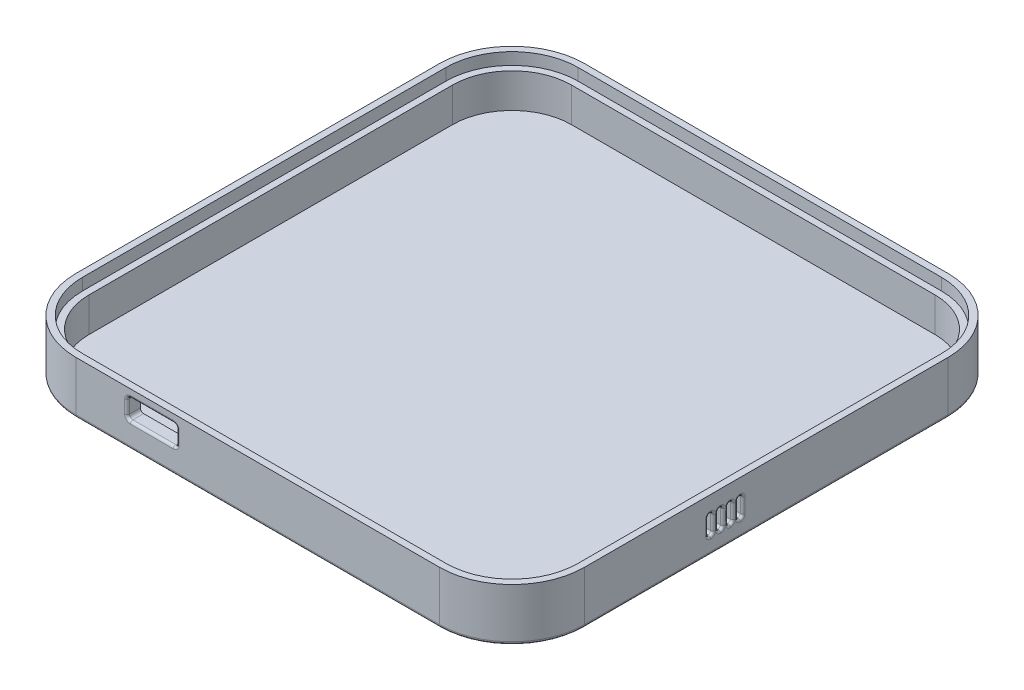
SolidWorks part; units mm, degrees
ref_plane "Front Plane" through (0, 0, 0) normal (0, 0, 1) x (1, 0, 0)
ref_plane "Top Plane" through (0, 0, 0) normal (0, 1, 0) x (1, 0, 0)
ref_plane "Right Plane" through (0, 0, 0) normal (1, 0, 0) x (0, 0, -1)
sketch "Sketch1" plane through (0, 0, 0) normal (0, 1, 0) x (1, 0, 0)
  line L0 (0, 75) -> (55, 75)
  line L1 (75, 55) -> (75, 0)
  line L2 (75, 0) -> (75, -55)
  line L3 (55, -75) -> (0, -75)
  line L4 (0, -75) -> (-55, -75)
  line L5 (-75, -55) -> (-75, 0)
  line L6 (-75, 0) -> (-75, 55)
  line L7 (-55, 75) -> (0, 75)
  line L8 (-55, 77) -> (0, 77)
  line L9 (0, 77) -> (55, 77)
  line L10 (77, 55) -> (77, 0)
  line L11 (77, 0) -> (77, -55)
  line L12 (55, -77) -> (0, -77)
  line L13 (0, -77) -> (-55, -77)
  line L14 (-77, -55) -> (-77, 0)
  line L15 (-77, 0) -> (-77, 55)
  arc A0 (55, 75) -> (75, 55) centre (55, 55) cw
  arc A1 (75, -55) -> (55, -75) centre (55, -55) cw
  arc A2 (-55, -75) -> (-75, -55) centre (-55, -55) cw
  arc A3 (-75, 55) -> (-55, 75) centre (-55, 55) cw
  arc A4 (55, 77) -> (77, 55) centre (55, 55) cw
  arc A5 (77, -55) -> (55, -77) centre (55, -55) cw
  arc A6 (-55, -77) -> (-77, -55) centre (-55, -55) cw
  arc A7 (-77, 55) -> (-55, 77) centre (-55, 55) cw
  point P24 (0, 0)
  dimension "D1" = 75
  dimension "D2" = 75
  dimension "D3" = 20
  dimension "D5" = 2
  dimension "D4" = 4
extrude "Boss-Extrude2" add sketch "Sketch1" along normal blind 14
sketch "Sketch4" plane through (0, 0, 0) normal (0, 1, 0) x (1, 0, 0)
  line L20 (55, 73) -> (-55, 73)
  line L21 (73, -55) -> (73, 55)
  line L22 (-55, -73) -> (55, -73)
  line L23 (-73, 55) -> (-73, -55)
  line L24 (55, 73) -> (-55, 73)
  line L25 (73, -55) -> (73, 55)
  line L26 (-55, -73) -> (55, -73)
  line L27 (-73, 55) -> (-73, -55)
  line L44 (55, 75) -> (-55, 75)
  line L45 (75, -55) -> (75, 55)
  line L46 (-55, -75) -> (55, -75)
  line L47 (-75, 55) -> (-75, -55)
  line L48 (55, 75) -> (-55, 75)
  line L49 (75, -55) -> (75, 55)
  line L50 (-55, -75) -> (55, -75)
  line L51 (-75, 55) -> (-75, -55)
  arc A24 (73, 55) -> (55, 73) centre (55, 55) ccw
  arc A25 (55, -73) -> (73, -55) centre (55, -55) ccw
  arc A26 (-73, -55) -> (-55, -73) centre (-55, -55) ccw
  arc A27 (-55, 73) -> (-73, 55) centre (-55, 55) ccw
  arc A28 (73, 55) -> (55, 73) centre (55, 55) ccw
  arc A29 (55, -73) -> (73, -55) centre (55, -55) ccw
  arc A30 (-73, -55) -> (-55, -73) centre (-55, -55) ccw
  arc A31 (-55, 73) -> (-73, 55) centre (-55, 55) ccw
  arc A52 (75, 55) -> (55, 75) centre (55, 55) ccw
  arc A53 (55, -75) -> (75, -55) centre (55, -55) ccw
  arc A54 (-75, -55) -> (-55, -75) centre (-55, -55) ccw
  arc A55 (-55, 75) -> (-75, 55) centre (-55, 55) ccw
  arc A56 (75, 55) -> (55, 75) centre (55, 55) ccw
  arc A57 (55, -75) -> (75, -55) centre (55, -55) ccw
  arc A58 (-75, -55) -> (-55, -75) centre (-55, -55) ccw
  arc A59 (-55, 75) -> (-75, 55) centre (-55, 55) ccw
  dimension "D1" = 2
  dimension "D2" = 0
extrude "Boss-Extrude3" add sketch "Sketch4" along normal blind 10.4
sketch "Sketch5" plane through (0, 0, 0) normal (0, -1, 0) x (1, 0, 0)
  line L8 (-55, -77) -> (55, -77)
  line L9 (77, -55) -> (77, 55)
  line L10 (55, 77) -> (-55, 77)
  line L11 (-77, 55) -> (-77, -55)
  line L12 (-55, -77) -> (55, -77)
  line L13 (77, -55) -> (77, 55)
  line L14 (55, 77) -> (-55, 77)
  line L15 (-77, 55) -> (-77, -55)
  arc A8 (-77, -55) -> (-55, -77) centre (-55, -55) ccw
  arc A9 (55, -77) -> (77, -55) centre (55, -55) ccw
  arc A10 (77, 55) -> (55, 77) centre (55, 55) ccw
  arc A11 (-55, 77) -> (-77, 55) centre (-55, 55) ccw
  arc A12 (-77, -55) -> (-55, -77) centre (-55, -55) ccw
  arc A13 (55, -77) -> (77, -55) centre (55, -55) ccw
  arc A14 (77, 55) -> (55, 77) centre (55, 55) ccw
  arc A15 (-55, 77) -> (-77, 55) centre (-55, 55) ccw
  dimension "D1" = 0
extrude "Boss-Extrude4" add sketch "Sketch5" along normal blind 2
sketch "Sketch6" plane through (0, 0, 77) normal (0, 0, 1) x (1, 0, 0)
  line L0 (-77, 14) -> (-77, -2) construction
  line L1 (-39.5, 5.5) -> (-24.5, 5.5)
  line L2 (-39.5, 5.5) -> (-39.5, 11.5)
  line L3 (-39.5, 11.5) -> (-24.5, 11.5)
  line L4 (-24.5, 5.5) -> (-24.5, 11.5)
  line L5 (-39.5, 5.5) -> (-24.5, 11.5) construction
  line L6 (-39.5, 11.5) -> (-24.5, 5.5) construction
  line L7 (55, -2) -> (-55, -2) construction
  point P0 (-32, 8.5)
  dimension "D1" = 15
  dimension "D2" = 45
  dimension "D3" = 10.5
  dimension "D4" = 6
extrude "Cut-Extrude1" cut sketch "Sketch6" against normal up to next
fillet "Fillet1" radius 1 4 edges at (-39.5, 5.5, 75) (-24.5, 5.5, 75) (-24.5, 11.5, 76) (-39.5, 11.5, 76)
sketch "Sketch7" plane through (77, 0, 0) normal (1, 0, 0) x (0, 0, -1)
  line L0 (-13.15, 8.9478) -> (-13.15, 3.0522)
  line L1 (-17.65, 8.9478) -> (-16.15, 8.9478)
  line L2 (-17.65, 8.9478) -> (-17.65, 3.0522)
  line L3 (-17.65, 3.0522) -> (-16.15, 3.0522)
  line L4 (-16.15, 8.9478) -> (-16.15, 3.0522)
  line L5 (-14.65, 8.9478) -> (-13.15, 8.9478)
  line L6 (-14.65, 8.9478) -> (-14.65, 3.0522)
  line L7 (-14.65, 3.0522) -> (-13.15, 3.0522)
  line L8 (-10.15, 8.9478) -> (-10.15, 3.0522)
  line L9 (-11.65, 8.9478) -> (-10.15, 8.9478)
  line L10 (-11.65, 8.9478) -> (-11.65, 3.0522)
  line L11 (-11.65, 3.0522) -> (-10.15, 3.0522)
  line L12 (-7.15, 8.9478) -> (-7.15, 3.0522)
  line L13 (-8.65, 8.9478) -> (-7.15, 8.9478)
  line L14 (-8.65, 8.9478) -> (-8.65, 3.0522)
  line L15 (-8.65, 3.0522) -> (-7.15, 3.0522)
  line L16 (-13.15, 6) -> (-11.65, 6) construction
  line L17 (-14.65, 6) -> (-16.15, 6) construction
  line L18 (-10.15, 6) -> (-8.65, 6) construction
  line L19 (-77, 14) -> (-77, -2) construction
  line L20 (-55, 14) -> (55, 14) construction
  point P22 (-12.4, 6)
  dimension "D1" = 1.5
  dimension "D3" = 64.6
  dimension "D4" = 8
  dimension "D2" = 4
extrude "Cut-Extrude2" cut sketch "Sketch7" against normal up to next
fillet "Fillet2" radius 0.75 32 edges at (73, 6, 7.15) (77, 6, 7.15) (73, 6, 10.15) (77, 6, 10.15) (73, 6, 13.15) (77, 6, 13.15) (73, 6, 16.15) (77, 6, 16.15) (75, 8.9478, 7.15) (73, 6, 8.65) (75, 3.0522, 8.65) (77, 6, 8.65) (75, 8.9478, 8.65) (75, 8.9478, 10.15) (73, 6, 11.65) (75, 3.0522, 11.65) (77, 6, 11.65) (75, 8.9478, 11.65) (75, 8.9478, 13.15) (73, 6, 14.65) (75, 3.0522, 14.65) (77, 6, 14.65) (75, 8.9478, 14.65) (73, 6, 17.65) (75, 3.0522, 17.65) (77, 6, 17.65) (75, 8.9478, 17.65) (75, 8.9478, 16.15) (75, 3.0522, 7.15) (75, 3.0522, 10.15) (75, 3.0522, 13.15) (75, 3.0522, 16.15)
fillet "Fillet3" radius 0.75 8 edges at (-24.7929, 11.2071, 77) (-24.5, 8.5, 77) (-24.7929, 5.7929, 77) (-32, 5.5, 77) (-39.2071, 5.7929, 77) (-39.5, 8.5, 77) (-39.2071, 11.2071, 77) (-32, 11.5, 77)
fillet "Fillet4" radius 1 8 edges at (70.5563, -2, 70.5563) (77, -2, 0) (70.5563, -2, -70.5563) (0, -2, -77) (-70.5563, -2, -70.5563) (-77, -2, 0) (-70.5563, -2, 70.5563) (0, -2, 77)
